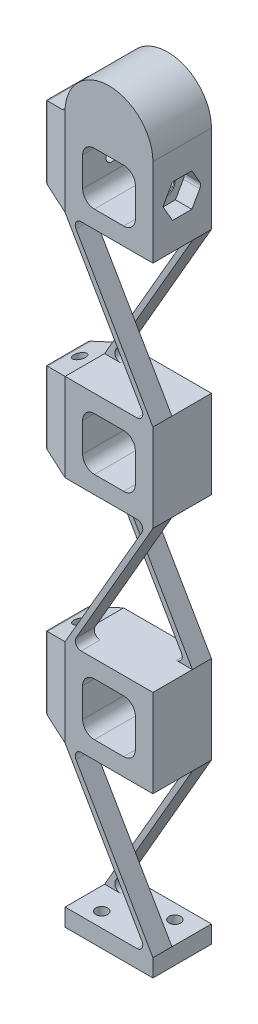
SolidWorks part; units mm, degrees
material "PET"
ref_plane "Front Plane" through (0, 0, 0) normal (0, 0, 1) x (1, 0, 0)
ref_plane "Top Plane" through (0, 0, 0) normal (0, 1, 0) x (1, 0, 0)
ref_plane "Right Plane" through (0, 0, 0) normal (1, 0, 0) x (0, 0, -1)
sketch "Sketch1" plane through (0, 0, 0) normal (0, 0, 1) x (1, 0, 0)
  line L0 (0, 0) -> (57.9688, 0) construction
  line L1 (7.5, 12.1244) -> (-7.5, 12.1244)
  line L2 (7.5, -27.1244) -> (-7.5, -27.1244)
  line L3 (7.5, -27.1244) -> (7.5, -12.1244)
  line L4 (7.5, -12.1244) -> (-7.5, -12.1244)
  line L5 (-7.5, -27.1244) -> (-7.5, -12.1244)
  line L6 (7.5, -27.1244) -> (-7.5, -12.1244) construction
  line L7 (7.5, -12.1244) -> (-7.5, -27.1244) construction
  line L8 (-7.5, 27.1244) -> (-7.5, 12.1244)
  line L9 (0, 0) -> (0, 41.5625) construction
  line L10 (7.5, 27.1244) -> (-7.5, 27.1244)
  line L11 (7.5, 27.1244) -> (7.5, 12.1244)
  line L12 (-7.5, 12.1244) -> (6.5, -12.1244)
  line L13 (6.5, -12.1244) -> (7.5, -12.1244)
  line L14 (7.5, -12.1244) -> (-6.5, 12.1244)
  line L15 (-6.5, 12.1244) -> (-7.5, 12.1244)
  line L16 (7.5, 12.1244) -> (-6.5, -12.1244)
  line L17 (-7.5, -12.1244) -> (6.5, 12.1244)
  point P1 (0, -19.6244)
  dimension "D1" = 15
  dimension "D2" = 60
extrude "Boss-Extrude1" add sketch "Sketch1" along normal mid plane 10 contours L5 L2 L3 L4 region at (0, -19.6244, 0)
extrude "Boss-Extrude2" add sketch "Sketch1<3>" against normal blind 3.25 from surface contours L17 L4 L16 L12 | L17 L14 L16 L1 | L17 L12 L16 L14 region at (3.6296, 6.276, 0) region at (0, 0, 0) region at (-3.6296, -6.276, 0) starting at face at (0, -19.6244, 5)
sketch "Sketch1<3>" plane through (0, 0, 0) normal (0, 0, 1) x (1, 0, 0) same geometry as "Sketch1"
extrude "Boss-Extrude3" add sketch "Sketch1<4>" along normal blind 3.25 from surface contours L12 L17 L14 L1 | L14 L16 L12 L4 | L17 L12 L16 L14 region at (0, 0, 0) region at (3.6296, -6.276, 0) region at (-3.6296, 6.276, 0) starting at face at (0, -19.6244, -5)
sketch "Sketch1<4>" plane through (0, 0, 0) normal (0, 0, 1) x (1, 0, 0) same geometry as "Sketch1"
extrude "Boss-Extrude4" add sketch "Sketch1<5>" along normal mid plane 10 contours L11 L10 L8 L1 region at (0, 19.6244, 0)
sketch "Sketch1<5>" plane through (0, 0, 0) normal (0, 0, 1) x (1, 0, 0) same geometry as "Sketch1"
ref_plane "Plane1" through (0, 19.6244, 0) normal (0, -1, 0) x (-1, 0, 0)
ref_plane "Plane2" through (7.5, -27.1244, 5) normal (-1, 0, 0) x (0, 0, 1)
ref_plane "Plane3" through (0, -19.6244, 0) normal (0, 1, 0) x (1, 0, 0)
mirror "Mirror2" about plane through (0, 19.6244, 0) normal (0, -1, 0) of "Boss-Extrude2", "Boss-Extrude3"
mirror "Mirror3" about plane through (0, 19.6244, 0) normal (0, -1, 0) of "Boss-Extrude1"
mirror "Mirror4" about plane through (0, -19.6244, 0) normal (0, 1, 0) of "Boss-Extrude2"
mirror "Mirror5" about plane through (0, -19.6244, 0) normal (0, 1, 0) of "Boss-Extrude3"
mirror "Mirror6" about plane through (0, -19.6244, 0) normal (0, 1, 0) of "Boss-Extrude4"
sketch "Sketch29" plane through (0, 0, 5) normal (0, 0, 1) x (1, 0, 0)
  line L0 (7.5, 66.3731) -> (-7.5, 66.3731) construction
  line L1 (7.5, 66.3731) -> (-7.5, 66.3731)
  arc A0 (-7.5, 66.3731) -> (7.5, 66.3731) centre (0, 66.3731) cw
  line M10 (7.5, 66.3731) -> (-7.5, 66.3731)
extrude "Boss-Extrude5" add sketch "Sketch29" against normal up to surface (10 mm away) contours A0 M10 region at (0, 69.5562, 5) up to face at (0, 0, -5)
ref_plane "Plane4" through (0, -54.3731, 0) normal (0, 1, 0) x (1, 0, 0)
sketch "Sketch36" plane through (0, -54.3731, 0) normal (0, 1, 0) x (1, 0, 0)
  line L4 (7.5, -5) -> (7.5, 5)
  line L5 (7.5, 5) -> (-7.5, 5)
  line L6 (-7.5, 5) -> (-7.5, -5)
  line L7 (-7.5, -5) -> (7.5, -5)
  line L8 (7.5, -5) -> (7.5, 5)
  line L9 (7.5, 5) -> (-7.5, 5)
  line L10 (-7.5, 5) -> (-7.5, -5)
  line L11 (-7.5, -5) -> (7.5, -5)
  dimension "D1" = 0
extrude "Cut-Extrude1" cut sketch "Sketch36" against normal through all
fillet "Fillet1" radius 1 12 edges at (-6.5, -12.1244, 3.375) (6.5, -12.1244, -3.375) (-6.5, 12.1244, -3.375) (6.5, 12.1244, 3.375) (6.5, 51.3731, -3.375) (-6.5, 51.3731, 3.375) (6.5, 27.1244, 3.375) (-6.5, 27.1244, -3.375) (-6.5, -51.3731, -3.375) (6.5, -51.3731, 3.375) (6.5, -27.1244, -3.375) (-6.5, -27.1244, 3.375)
sketch "Sketch48" plane through (0, -51.3731, 0) normal (0, 1, 0) x (1, 0, 0)
  line L0 (0, 0) -> (-7.5, -5) construction
  line L1 (-7.5, -5) -> (7.5, -5) construction
  line L2 (0, 0) -> (-3.3333, 5) construction
  line L3 (7.5, 5) -> (-7.5, 5) construction
  circle A0 centre (-3.75, -2.5) radius 1
  circle A1 centre (3.75, 2.5) radius 1
  point P6 (-3.75, -2.5)
  point P9 (3.75, 2.5)
  dimension "D1" = 2
hole_wizard "Ø2.0 mm Dowel Holes1" positions "Sketch48" profile "Sketch49" hole size "Ø2.0" standard "DIN" end condition through all
sketch "Sketch49" plane through (3.75, -51.3731, -2.5) normal (1, 0, 0) x (0, 0, 1)
  line L0 (0, 0) -> (0, 3)
  line L1 (0, 3) -> (1, 3)
  line L2 (1, 3) -> (1, 0)
  line L5 (1, 0) -> (0, 0)
  line L11 (0, -6.35) -> (0, 107.95) construction
  dimension "Thru Hole Dia." = 2
  dimension "Thru Hole Depth" = 3
ref_plane "Plane5" through (0, 0, 0) normal (0, 0, 1) x (1, 0, 0)
ref_plane "finger_surface" through (-12.5, 0, 0) normal (-1, 0, 0) x (0, 0, 1)
sketch "Sketch82" plane through (-12.5, 0, 0) normal (-1, 0, 0) x (0, 0, 1)
  line L0 (-3.5, 64.8731) -> (-3.5, 52.8731)
  line L1 (-3.5, 52.8731) -> (1.75, 52.8731)
  line L2 (1.75, 52.8731) -> (3.5, 52.8731)
  line L3 (3.5, 52.8731) -> (3.5, 64.8731)
  line L4 (3.5, 64.8731) -> (-3.5, 64.8731)
  line L5 (-5, 66.3731) -> (-5, 51.3731)
  line L6 (-5, 51.3731) -> (1.75, 51.3731)
  line L7 (1.75, 51.3731) -> (5, 51.3731)
  line L8 (5, 51.3731) -> (5, 66.3731)
  line L9 (5, 66.3731) -> (-5, 66.3731)
  line L10 (-5, 66.3731) -> (-5, 51.3731)
  line L11 (-5, 51.3731) -> (1.75, 51.3731)
  line L12 (1.75, 51.3731) -> (5, 51.3731)
  line L13 (5, 51.3731) -> (5, 66.3731)
  line L14 (5, 66.3731) -> (-5, 66.3731)
  dimension "D2" = 1.5
loft "Loft1" add section face at (-7.5, 57.3731, 0.35) section "Sketch82" connector at (-7.5, 66.3731, 5) connector at (-12.5, 64.8731, 3.5)
sketch "Sketch83" plane through (-12.5, 0, 0) normal (-1, 0, 0) x (0, 0, 1)
  line L0 (-3.5, 25.6244) -> (-3.5, 13.6244)
  line L1 (-3.5, 13.6244) -> (-1.75, 13.6244)
  line L2 (-1.75, 13.6244) -> (3.5, 13.6244)
  line L3 (3.5, 13.6244) -> (3.5, 25.6244)
  line L4 (3.5, 25.6244) -> (-1.75, 25.6244)
  line L5 (-1.75, 25.6244) -> (-3.5, 25.6244)
  line L6 (-5, 27.1244) -> (-5, 12.1244)
  line L7 (-5, 12.1244) -> (-1.75, 12.1244)
  line L8 (-1.75, 12.1244) -> (5, 12.1244)
  line L9 (5, 12.1244) -> (5, 27.1244)
  line L10 (5, 27.1244) -> (-1.75, 27.1244)
  line L11 (-1.75, 27.1244) -> (-5, 27.1244)
  line L12 (-5, 27.1244) -> (-5, 12.1244)
  line L13 (-5, 12.1244) -> (-1.75, 12.1244)
  line L14 (-1.75, 12.1244) -> (5, 12.1244)
  line L15 (5, 12.1244) -> (5, 27.1244)
  line L16 (5, 27.1244) -> (-1.75, 27.1244)
  line L17 (-1.75, 27.1244) -> (-5, 27.1244)
  line L18 (-5, -12.1244) -> (-5, -27.1244)
  line L19 (-5, -27.1244) -> (1.75, -27.1244)
  line L20 (1.75, -27.1244) -> (5, -27.1244)
  line L21 (5, -27.1244) -> (5, -12.1244)
  line L22 (5, -12.1244) -> (1.75, -12.1244)
  line L23 (1.75, -12.1244) -> (-5, -12.1244)
  line L24 (-5, -12.1244) -> (-5, -27.1244)
  line L25 (-5, -27.1244) -> (1.75, -27.1244)
  line L26 (1.75, -27.1244) -> (5, -27.1244)
  line L27 (5, -27.1244) -> (5, -12.1244)
  line L28 (5, -12.1244) -> (1.75, -12.1244)
  line L29 (1.75, -12.1244) -> (-5, -12.1244)
  line L30 (-3.5, -13.6244) -> (-3.5, -25.6244)
  line L31 (-3.5, -25.6244) -> (1.75, -25.6244)
  line L32 (1.75, -25.6244) -> (3.5, -25.6244)
  line L33 (3.5, -25.6244) -> (3.5, -13.6244)
  line L34 (3.5, -13.6244) -> (1.75, -13.6244)
  line L35 (1.75, -13.6244) -> (-3.5, -13.6244)
  dimension "D3" = 1.5
  dimension "D4" = 1.5
loft "Loft2" add section face at (-7.5, 19.6244, -0.5833) section "Sketch83" connector at (-7.5, 27.1244, 5) connector at (-12.5, 25.6244, 3.5)
sketch "Sketch84" plane through (-12.5, 0, 0) normal (-1, 0, 0) x (0, 0, 1)
  line L0 (-3.5, -13.6244) -> (-3.5, -25.6244)
  line L1 (-3.5, -25.6244) -> (1.75, -25.6244)
  line L2 (1.75, -25.6244) -> (3.5, -25.6244)
  line L3 (3.5, -25.6244) -> (3.5, -13.6244)
  line L4 (3.5, -13.6244) -> (1.75, -13.6244)
  line L5 (1.75, -13.6244) -> (-3.5, -13.6244)
  line L6 (-5, -12.1244) -> (-5, -27.1244)
  line L7 (-5, -27.1244) -> (1.75, -27.1244)
  line L8 (1.75, -27.1244) -> (5, -27.1244)
  line L9 (5, -27.1244) -> (5, -12.1244)
  line L10 (5, -12.1244) -> (1.75, -12.1244)
  line L11 (1.75, -12.1244) -> (-5, -12.1244)
  line L12 (-5, -12.1244) -> (-5, -27.1244)
  line L13 (-5, -27.1244) -> (1.75, -27.1244)
  line L14 (1.75, -27.1244) -> (5, -27.1244)
  line L15 (5, -27.1244) -> (5, -12.1244)
  line L16 (5, -12.1244) -> (1.75, -12.1244)
  line L17 (1.75, -12.1244) -> (-5, -12.1244)
  dimension "D2" = 1.5
loft "Loft3" add section face at (-7.5, -19.6244, 0.5833) section "Sketch84" connector at (-7.5, -12.1244, 5) connector at (-12.5, -13.6244, 3.5)
sketch "Sketch97" plane through (7.5, 0, 0) normal (1, 0, 0) x (0, 0, -1)
  line L0 (-5, 66.3731) -> (5, 51.3731) construction
  line L1 (5, 66.3731) -> (-5, 51.3731) construction
  line L2 (-5, 66.3731) -> (5, 66.3731) construction
  line L3 (-1.6454, 61.7231) -> (-3.2909, 58.8731)
  line L4 (-3.2909, 58.8731) -> (-1.6454, 56.0231)
  line L5 (-1.6454, 56.0231) -> (1.6454, 56.0231)
  line L6 (1.6454, 56.0231) -> (3.2909, 58.8731)
  line L7 (3.2909, 58.8731) -> (1.6454, 61.7231)
  line L8 (1.6454, 61.7231) -> (-1.6454, 61.7231)
  circle A0 centre (0, 58.8731) radius 2.85 construction
  point P8 (0, 58.8731)
  dimension "D1" = 5.7
extrude "hex_nut M3" cut sketch "Sketch97" against normal blind 2.8
sketch "Sketch98" plane through (4.7, 0, 0) normal (1, 0, 0) x (0, 0, -1)
  line L0 (-1.6454, 61.7231) -> (1.6454, 56.0231) construction
  line L1 (1.6454, 61.7231) -> (-1.6454, 56.0231) construction
  circle A0 centre (0, 58.8731) radius 1.6
  point P8 (0, 58.8731)
  dimension "D1" = 3.2
extrude "Cut-Extrude5" cut sketch "Sketch98" against normal blind 8
sketch "Sketch99" plane through (0, 0, 0) normal (0, 0, 1) x (1, 0, 0)
  line L0 (7.5, 66.3731) -> (7.5, 51.3731) construction
  line L1 (-12.5, 52.8731) -> (-12.5, 64.8731) construction
  line L2 (7.5, 66.3731) -> (7.5, 51.3731) construction
  line L3 (-12.5, 52.8731) -> (-12.5, 64.8731) construction
  line L4 (-7.5, -54.3731) -> (7.5, -54.3731) construction
  line L5 (-7.5, -54.3731) -> (7.5, -54.3731) construction
  line L6 (7.5, 58.8731) -> (-7, 58.8731)
  line L7 (-10, 55.8731) -> (-10, -54.3731)
  arc A0 (-7, 58.8731) -> (-10, 55.8731) centre (-7, 55.8731) ccw
  dimension "D2" = 3
  dimension "D1" = 5
sweep "tendon_path" cut path "Sketch99" circular profile diameter 2 parameters "D3"=2
fillet "Fillet5" radius 1 1 edges at (-3.3, 59.8731, 0)
fillet "Fillet6" radius 1 19 edges at (-7.5, 66.3731, 0) (6.1, 58.8731, -3.2909)
sketch "Sketch111" plane through (0, 0, 5) normal (0, 0, 1) x (1, 0, 0)
  line L0 (-7.5, -12.1244) -> (7.5, -12.1244)
  line L1 (-7.5, -12.1244) -> (-7.5, -27.1244)
  line L2 (-7.5, -27.1244) -> (7.5, -27.1244)
  line L3 (7.5, -23.7507) -> (7.5, -30.498) construction
  line L4 (7.5, -27.1244) -> (7.5, -12.1244) construction
  line L5 (7.5, -27.1244) -> (7.5, -12.1244)
  line L6 (17.5, -37.1244) -> (17.5, -2.1244)
  line L7 (-17.5, -2.1244) -> (17.5, -2.1244)
  line L8 (-17.5, -2.1244) -> (-17.5, -37.1244)
  line L9 (-17.5, -37.1244) -> (17.5, -37.1244)
  line L10 (-4.5, -17.1244) -> (-4.5, -22.1244)
  line L11 (-2.5, -24.1244) -> (2.5, -24.1244)
  line L12 (4.5, -22.1244) -> (4.5, -17.1244)
  line L13 (-2.5, -15.1244) -> (2.5, -15.1244)
  line L14 (-4.5, -15.1244) -> (-4.5, -24.1244) construction
  line L15 (-4.5, -24.1244) -> (4.5, -24.1244) construction
  line L16 (4.5, -24.1244) -> (4.5, -15.1244) construction
  line L17 (-4.5, -15.1244) -> (4.5, -15.1244) construction
  arc A0 (-4.5, -22.1244) -> (-2.5, -24.1244) centre (-2.5, -22.1244) ccw
  arc A1 (2.5, -24.1244) -> (4.5, -22.1244) centre (2.5, -22.1244) ccw
  arc A2 (4.5, -17.1244) -> (2.5, -15.1244) centre (2.5, -17.1244) ccw
  arc A3 (-4.5, -17.1244) -> (-2.5, -15.1244) centre (-2.5, -17.1244) cw
  dimension "D3" = 2
  dimension "D1" = 10
  dimension "D2" = 3
extrude "Cut-Extrude6" cut sketch "Sketch111" against normal up to surface (10 mm away) contours A3 L10 A0 L11 A1 L12 A2 L13 region at (0, -19.6244, 5) up to face at (-0.2465, 3.4033, -5)
pattern_linear "LPattern1" count 3 spacing 39.2487 along (0, 1, 0) of "Cut-Extrude6"
equation "\"a\"= 3.25"
equation "\"D1@Boss-Extrude2\"=\"a\""
equation "\"D1@Boss-Extrude3\"= \"a\""
equation "\"d_sheath\"= 3.5'M2 threaded inserts"
equation "\"r\"= 3.2'radius for tendon routing"
equation "\"angle\"= 60deg'angle of cross flexures"
equation "\"side_length\"= 15mm"
equation "\"d\"= \"side_length\" + \"d1\"'for linear patterns"
equation "\"w\"= 1mm'width of the cross flexures"
equation "\"d1\"= tan ( \"angle\" ) * \"diff\"'dist between top face and bottom face of 2 consecutive fingers"
equation "\"diff\"= \"side_length\" - \"w\""
equation "\"D3@Sketch1\"=\"w\""
equation "\"D2@Sketch1\"=\"angle\""
equation "\"offset\"= 1.5'loft offset for finger surface"
equation "\"D2@Sketch82\"=\"offset\""
equation "\"D3@Sketch83\"=\"offset\""
equation "\"D4@Sketch83\"=\"offset\""
equation "\"D2@Sketch84\"=\"offset\""
equation "\"D3@LPattern1\"=\"d\""
